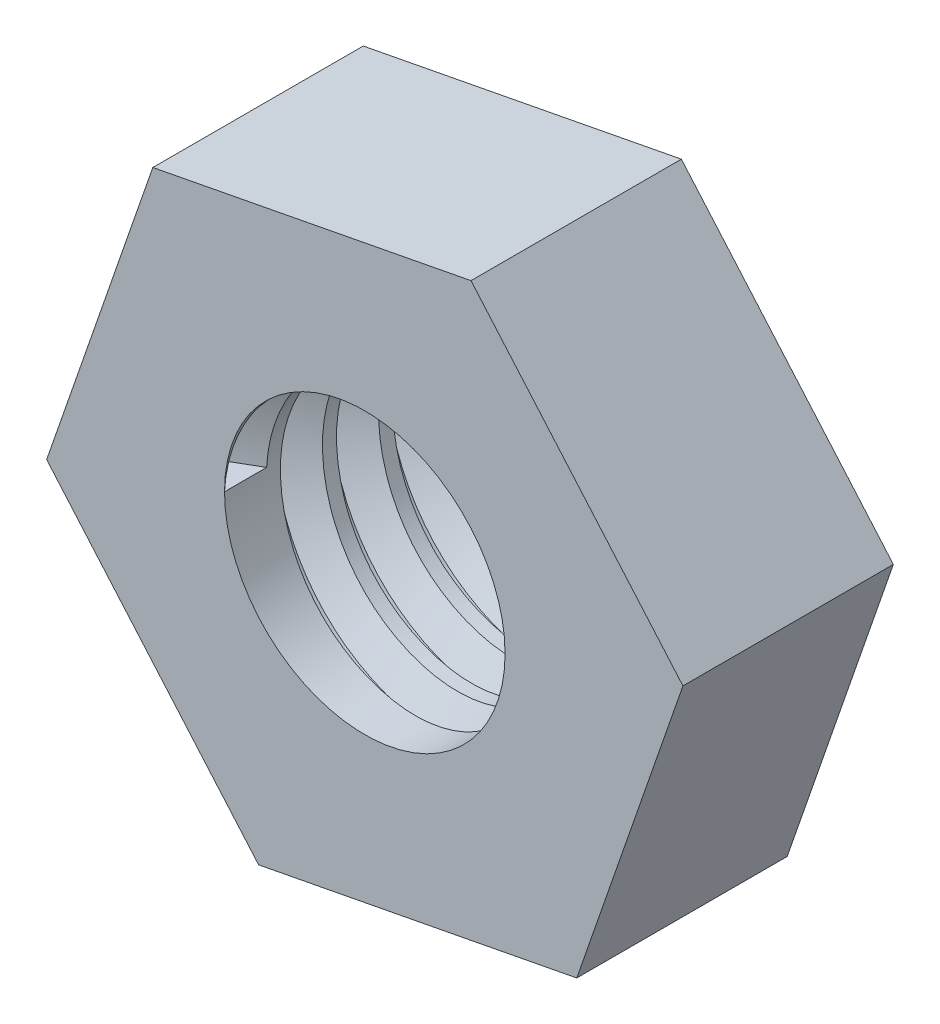
SolidWorks part; units mm, degrees
ref_plane "Front Plane" through (0, 0, 0) normal (0, 0, 1) x (1, 0, 0)
ref_plane "Top Plane" through (0, 0, 0) normal (0, 1, 0) x (1, 0, 0)
ref_plane "Right Plane" through (0, 0, 0) normal (1, 0, 0) x (0, 0, -1)
sketch "Sketch1" plane through (0, 0, 0) normal (0, 0, 1) x (1, 0, 0)
  line L1 (1.511, -1.7465) -> (2.268, 0.4354)
  line L2 (2.268, 0.4354) -> (0.757, 2.1818)
  line L3 (0.757, 2.1818) -> (-1.511, 1.7465)
  line L4 (-1.511, 1.7465) -> (-2.268, -0.4354)
  line L5 (-2.268, -0.4354) -> (-0.757, -2.1818)
  line L6 (-0.757, -2.1818) -> (1.511, -1.7465)
  circle A0 centre (0, 0) radius 2 construction
  dimension "D2" = 4
extrude "Boss-Extrude1" add sketch "Sketch1" along normal blind 1.5
sketch "Sketch2" plane through (0, 0, 1.5) normal (0, 0, 1) x (1, 0, 0)
  circle A0 centre (0, 0) radius 1
  dimension "D1" = 2
extrude "Cut-Extrude1" cut sketch "Sketch2" against normal through all
thread "Thread1" pitch 0.4 method cut profile "Thread Profile1" start angle 0, offset 0, length 0, pitch 0.4, diameter 2
ref_plane "Plane1" through (-1, 0, 1.5) normal (0, -1, 0) x (-1, 0, 0)
sketch "Thread Profile1" plane through (-1, 0, 1.5) normal (0, -1, 0) x (-1, 0, 0)
  line L0 (0, 0) -> (0, 0.4) construction
  line L1 (0, 0) -> (0.2165, 0.125)
  line L2 (0.2165, 0.125) -> (0.2165, 0.175)
  line L3 (0.2165, 0.175) -> (0, 0.3)
  line L4 (0.2165, 0.15) -> (0, 0.15) construction
  line L11 (0, 0) -> (0, 0.3)
  point P2 (0, 0)
  dimension "Pitch" = 0.4
  dimension "Profile_Angle" = 60
  dimension "Profile_Land" = 0.05
  dimension "Profile_Height" = 0.2165
